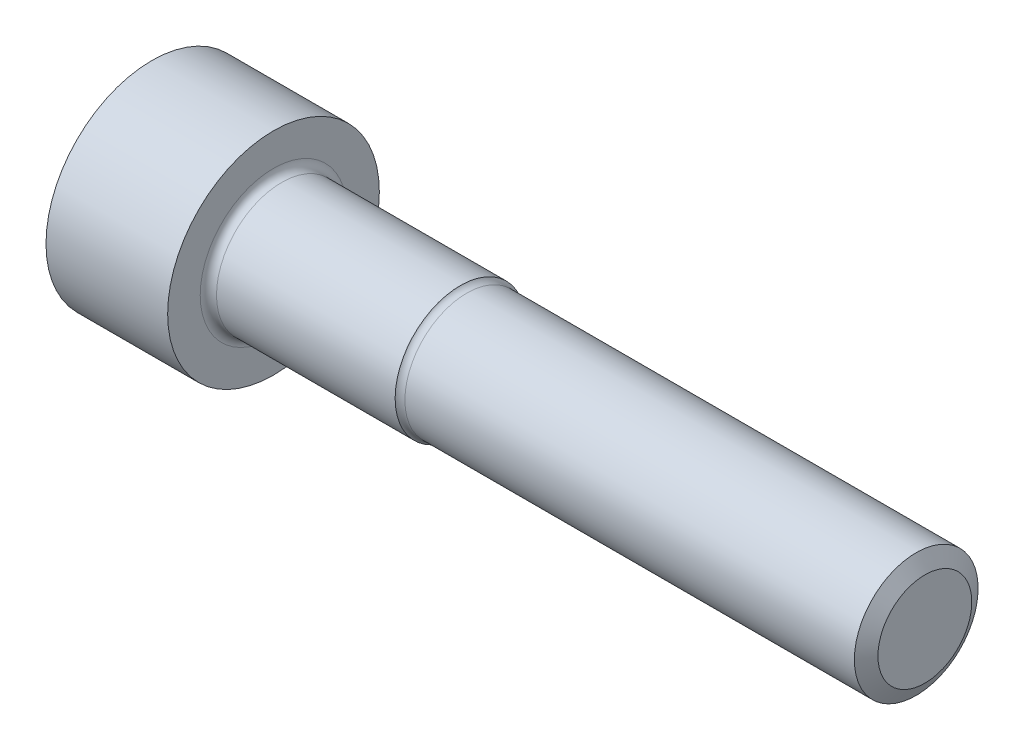
SolidWorks part; units mm, degrees
ref_plane "Płaszczyzna przednia" through (0, 0, 0) normal (0, 0, 1) x (1, 0, 0)
ref_plane "Płaszczyzna górna" through (0, 0, 0) normal (0, 1, 0) x (1, 0, 0)
ref_plane "Płaszczyzna prawa" through (0, 0, 0) normal (1, 0, 0) x (0, 0, -1)
sketch "Szkic1" plane through (0, 0, 0) normal (0, 0, 1) x (1, 0, 0)
  line L0 (0, 0) -> (0, 5.582)
  line L1 (0, 5.582) -> (0.53, 6.5)
  line L2 (0.53, 6.5) -> (8, 6.5)
  line L3 (8, 6.5) -> (8, 4)
  line L10 (47.47, 3.8) -> (48, 2.882)
  line L11 (48, 2.882) -> (48, 0)
  line L12 (0, 0) -> (48, 0)
  line L13 (47.47, 3.8) -> (19.47, 3.8)
  line L14 (19.47, 3.8) -> (19.47, 4)
  line L15 (19.47, 4) -> (8, 4)
  dimension "D2" = 6.5
  dimension "D3" = 8
  dimension "D4" = 4
  dimension "D5" = 40
  dimension "D6" = 28
  dimension "D7" = 150
  dimension "D8" = 0.53
  dimension "D9" = 3.8
  dimension "D12" = 150
  dimension "D13" = 0.53
revolve "Obrót1" add sketch "Szkic1" angle 360 about L12
sketch "Szkic2" plane through (0, 0, 0) normal (-1, 0, 0) x (0, 0, 1)
  line L1 (0, -3.4641) -> (3, -1.7321)
  line L2 (3, -1.7321) -> (3, 1.7321)
  line L3 (3, 1.7321) -> (0, 3.4641)
  line L4 (0, 3.4641) -> (-3, 1.7321)
  line L5 (-3, 1.7321) -> (-3, -1.7321)
  line L6 (-3, -1.7321) -> (0, -3.4641)
  circle A0 centre (0, 0) radius 3 construction
  dimension "D1" = 6
extrude "Wytnij-wyciągnięcie1" cut sketch "Szkic2" against normal blind 4
sketch "Szkic3" plane through (0, 0, 0) normal (0, 0, 1) x (1, 0, 0)
  line L0 (-0.9028, 0) -> (4.8749, 0) construction
  line L3 (4, 0) -> (4, 3.4641)
  line L4 (4, 3.4641) -> (5.6153, 0)
  line L8 (5.6153, 0) -> (4, 0)
  dimension "D2" = 25
  dimension "D4" = 5.7777
  dimension "D5" = 4
  dimension "D6" = 0.9028
revolve "Wycięcie-obrót1" cut sketch "Szkic3" angle 360 about L0
fillet "Zaokrąglenie1" radius 0.5 2 edges at (19.47, 0, 3.8) (8, 0, 4)
